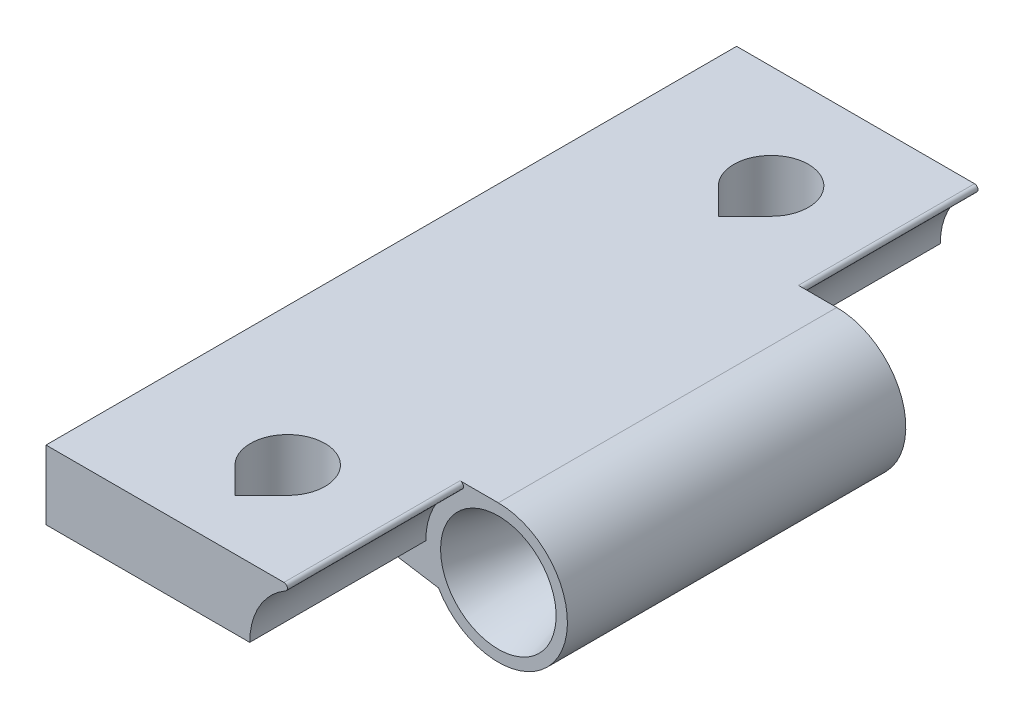
SolidWorks part; units mm, degrees
ref_plane "Front Plane" through (0, 0, 0) normal (0, 0, 1) x (1, 0, 0)
ref_plane "Top Plane" through (0, 0, 0) normal (0, 1, 0) x (1, 0, 0)
ref_plane "Right Plane" through (0, 0, 0) normal (1, 0, 0) x (0, 0, -1)
ref_plane "Plane1" through (0, 0, -25) normal (0, 0, -1) x (-1, 0, 0)
sketch "Sketch1" plane through (0, 0, -25) normal (0, 0, -1) x (-1, 0, 0)
  line L0 (5.25, 0) -> (20, 0)
  line L1 (20, 0) -> (20, 5)
  line L2 (20, 5) -> (2.7726, 5)
  arc A0 (2.7726, 5) -> (2.6466, 4.5341) centre (2.7726, 4.75) ccw
  arc A1 (2.6466, 4.5341) -> (5.25, 0) centre (0, 0) cw
extrude "Boss-Extrude1" add sketch "Sketch1" against normal blind 12.75
sketch "Sketch2" plane through (0, 0, -12.25) normal (0, 0, 1) x (1, 0, 0)
  line L0 (-20, 5) -> (0, 5)
  line L1 (-4.3301, -2.5) -> (-20, 0)
  line L2 (-20, 0) -> (-20, 5)
  arc A0 (0, 5) -> (-4.3301, -2.5) centre (0, 0) cw
extrude "Boss-Extrude2" add sketch "Sketch2" along normal blind 24.5
sketch "Sketch3" plane through (0, 0, 12.25) normal (0, 0, 1) x (1, 0, 0)
  line L0 (-20, 5) -> (-2.7726, 5)
  line L1 (-5.25, 0) -> (-20, 0)
  line L2 (-20, 0) -> (-20, 5)
  arc A0 (-2.7726, 5) -> (-2.6466, 4.5341) centre (-2.7726, 4.75) cw
  arc A1 (-2.6466, 4.5341) -> (-5.25, 0) centre (0, 0) ccw
extrude "Boss-Extrude3" add sketch "Sketch3" along normal blind 12.75
sketch "Sketch4" plane through (0, 5, 0) normal (0, 1, 0) x (-1, 0, 0)
  line L0 (10, -13.6816) -> (8.0908, -15.5908)
  line L1 (11.9092, -15.5908) -> (10, -13.6816)
  arc A0 (8.0908, -15.5908) -> (11.9092, -15.5908) centre (10, -17.5) ccw
extrude "Cut-Extrude1" cut sketch "Sketch4" against normal through all
sketch "Sketch5" plane through (0, 5, 0) normal (0, 1, 0) x (-1, 0, 0)
  line L0 (10, 21.3184) -> (8.0908, 19.4092)
  line L1 (11.9092, 19.4092) -> (10, 21.3184)
  arc A0 (8.0908, 19.4092) -> (11.9092, 19.4092) centre (10, 17.5) ccw
extrude "Cut-Extrude2" cut sketch "Sketch5" against normal through all
ref_plane "Plane2" through (0, 0, 0) normal (0, -1, 0) x (1, 0, 0)
sketch "Sketch6" plane through (0, 0, 0) normal (0, -1, 0) x (1, 0, 0)
  line L0 (4.1829, 12.25) -> (0, 12.25)
  line L1 (0, 12.25) -> (0, -12.25)
  line L2 (0, -12.25) -> (4.1829, -12.25)
  line L3 (0, 12.25) -> (0, -12.25) construction
  arc A0 (4.1829, -12.25) -> (4.1829, 12.25) centre (43.0625, 0) cw
revolve "Cut-Revolve1" cut sketch "Sketch6" angle 360 about L3 reverse direction yes
fillet "Fillet2" radius 0.25 1 edges at (-20, 0, -18.625) tangent propagation no
